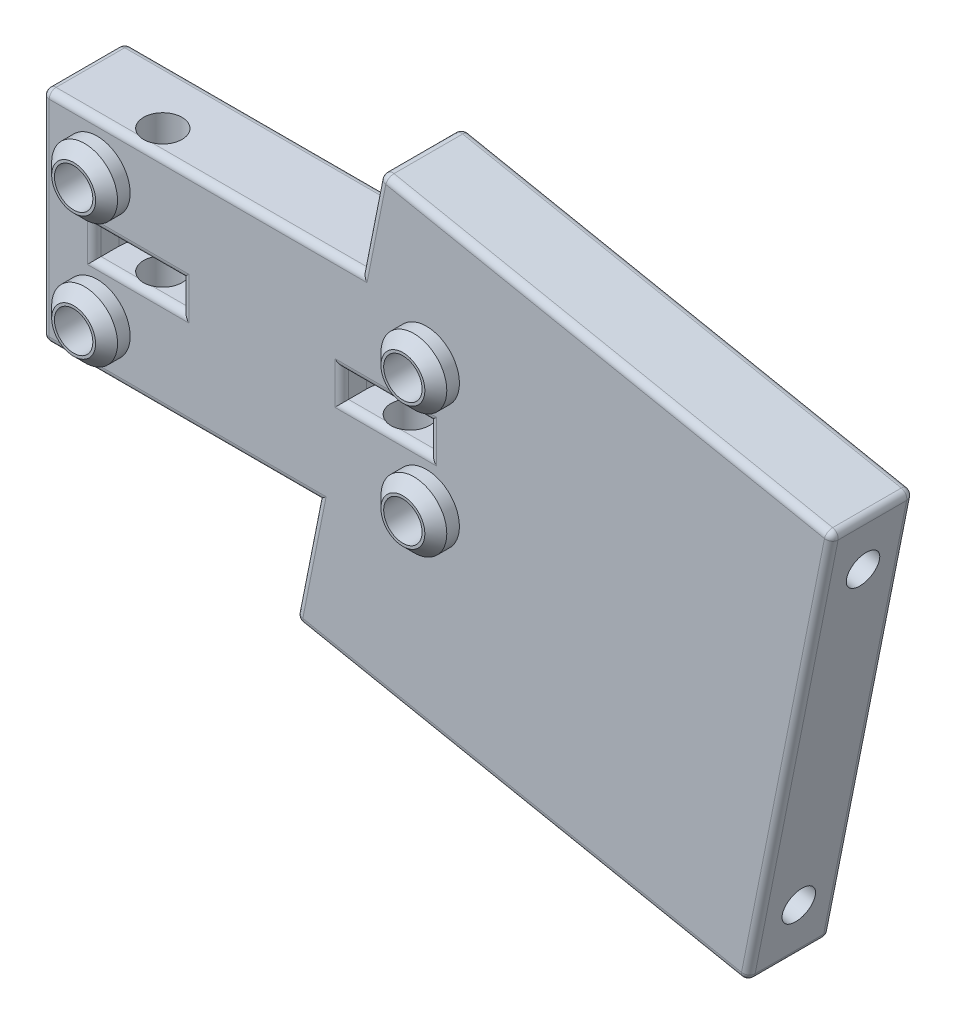
SolidWorks part; units mm, degrees
ref_plane "Front Plane" through (0, 0, 0) normal (0, 0, 1) x (1, 0, 0)
ref_plane "Top Plane" through (0, 0, 0) normal (0, 1, 0) x (1, 0, 0)
ref_plane "Right Plane" through (0, 0, 0) normal (1, 0, 0) x (0, 0, -1)
sketch "Sketch1" plane through (0, 0, 0) normal (0, 0, 1) x (1, 0, 0)
  line L2 (-38.1, -12.7) -> (-38.1, 12.7)
  line L3 (-38.1, 12.7) -> (38.1, 12.7)
  line L10 (38.1, -12.7) -> (38.1, 12.7)
  line L11 (-38.1, -12.7) -> (38.1, -12.7)
  line L14 (-38.1, 12.7) -> (38.1, -12.7) construction
  point P2 (0, 0)
  dimension "D1" = 76.2
  dimension "D2" = 25.4
extrude "Boss-Extrude1" add sketch "Sketch1" along normal blind 9.525
sketch "Sketch6" plane through (0, 0, 9.525) normal (0, 0, -1) x (-1, 0, 0)
  line L4 (8.8878, -26.0589) -> (-43.4272, -36.465)
  line L6 (8.8878, -26.0589) -> (-1.0228, 23.765)
  line L23 (-43.4272, -36.465) -> (-53.3378, 13.3589)
  line L24 (-1.0228, 23.765) -> (-53.3378, 13.3589)
  line L25 (8.8878, -26.0589) -> (-53.3378, 13.3589) construction
  line L26 (-43.4272, -36.465) -> (-1.0228, 23.765) construction
  line L27 (-38.1, 12.7) -> (38.1, 12.7) construction
  point P1 (-22.225, -6.35)
  dimension "D1" = 53.34
  dimension "D2" = 50.8
  dimension "D3" = 11.25
  dimension "D4" = 6.35
  dimension "D5" = 22.225
extrude "Boss-Extrude2" add sketch "Sketch6" along normal up to surface (9.525 mm away) up to face at (0, 0, 0)
sketch "Sketch4" plane through (0, 0, 0) normal (0, 1, 0) x (1, 0, 0)
  line L7 (-1.1782, -9.525) -> (-38.1, -9.525) construction
  line L8 (-32.0992, -6.6675) -> (-32.0992, -9.525)
  line L9 (-21.9392, -6.6675) -> (-21.9392, -9.525)
  line L10 (-21.9392, -9.525) -> (-32.0992, -9.525)
  line L11 (-38.1, -9.525) -> (-38.1, 0) construction
  arc A2 (-21.9392, -6.6675) -> (-32.0992, -6.6675) centre (-27.0192, -6.6675) ccw
  dimension "D1" = 10.16
  dimension "D2" = 2.8575
  dimension "D3" = 11.0808
extrude "Cut-Extrude2" cut sketch "Sketch4" against normal mid plane 3.302
ref_plane "Plane3" through (-12.7, 0, 0) normal (-1, 0, 0) x (0, 0, 1)
sketch "Sketch2" plane through (0, 0, 9.525) normal (0, 0, 1) x (1, 0, 0)
  line L1 (-38.1, 12.7) -> (-38.1, -12.7) construction
  line L2 (0, 0) -> (-38.1, 0) construction
  line L3 (-38.1, 12.7) -> (-38.1, -12.7) construction
  circle A0 centre (-31.75, 7.1755) radius 2.2225
  circle A1 centre (-31.75, -7.1755) radius 2.2225
  dimension "D1" = 4.445
  dimension "D2" = 14.351
  dimension "D3" = 6.35
extrude "Cut-Extrude1" cut sketch "Sketch2" against normal through all both and the other way through all
sketch "Sketch11" plane through (0, 0, 9.525) normal (0, 0, 1) x (1, 0, 0)
  circle A0 centre (-31.75, 7.1755) radius 3.81
  circle A1 centre (-31.75, 7.1755) radius 2.2225
  circle A2 centre (-31.75, 7.1755) radius 2.2225 construction
  circle A3 centre (-31.75, -7.1755) radius 3.81
  circle A4 centre (-31.75, -7.1755) radius 2.2225
  dimension "D1" = 7.62
extrude "Boss-Extrude5" add sketch "Sketch11" along normal blind 2.7305
sketch "Sketch5" plane through (0, 12.7, 0) normal (0, 1, 0) x (1, 0, 0)
  line L0 (-1.1782, -9.525) -> (-38.1, -9.525) construction
  line L1 (-38.1, -9.525) -> (-38.1, 0) construction
  circle A0 centre (-27.0192, -6.6675) radius 2.2225
  dimension "D3" = 4.445
  dimension "D1" = 2.8575
  dimension "D2" = 11.0808
extrude "Cut-Extrude3" cut sketch "Sketch5" against normal through all
mirror "Mirror1" about plane through (-12.7, 0, 0) normal (-1, 0, 0) of "Boss-Extrude5", "Cut-Extrude2", "Cut-Extrude3", "Cut-Extrude1"
chamfer "Chamfer4" distance 1.27 angle 45 4 edges at (-27.94, -7.1755, 12.2555) (2.54, -7.1755, 12.2555) (2.54, 7.1755, 12.2555) (-27.94, 7.1755, 12.2555)
fillet "Fillet3" radius 0.7937 30 edges at (-38.1, 0, 9.525) (-38.1, -12.7, 4.7625) (-38.1, 0, 0) (-38.1, 12.7, 4.7625) (-19.6391, 12.7, 0) (-19.6391, 12.7, 9.525) (-0.0777, 18.2325, 9.525) (-0.0777, 18.2325, 0) (1.0228, 23.765, 4.7625) (27.1803, 18.5619, 0) (27.1803, 18.5619, 9.525) (53.3378, 13.3589, 4.7625) (48.3825, -11.5531, 0) (48.3825, -11.5531, 9.525) (43.4272, -36.465, 4.7625) (17.2697, -31.2619, 0) (17.2697, -31.2619, 9.525) (-8.8878, -26.0589, 4.7625) (-7.5592, -19.3794, 9.525) (-7.5592, -19.3794, 0) (-22.1653, -12.7, 0) (-22.1653, -12.7, 9.525) (1.6193, -1.651, 9.525) (6.6993, 0, 9.525) (1.6193, 1.651, 9.525) (-3.4607, 0, 9.525) (-21.9392, 0, 9.525) (-32.0992, 0, 9.525) (-27.0192, 1.651, 9.525) (-27.0192, -1.651, 9.525)
sketch "Sketch12" plane through (48.7517, -9.6973, 0) normal (0.9808, -0.1951, 0) x (0, 0, -1)
  circle A6 centre (-4.7625, -20.9421) radius 1.905
  circle A7 centre (-4.7625, 17.1579) radius 1.905
  dimension "D1" = 3.81
extrude "Cut-Extrude4" cut sketch "Sketch12" against normal blind 9.525
sketch "Sketch13" plane through (-3.5634, 0.7088, 0) normal (-0.9808, 0.1951, 0) x (0, 0, 1)
  circle A0 centre (4.7625, 17.1579) radius 1.905
  circle A1 centre (4.7625, -20.9421) radius 1.905
  dimension "D1" = 3.81
extrude "Cut-Extrude5" cut sketch "Sketch13" against normal blind 9.525
